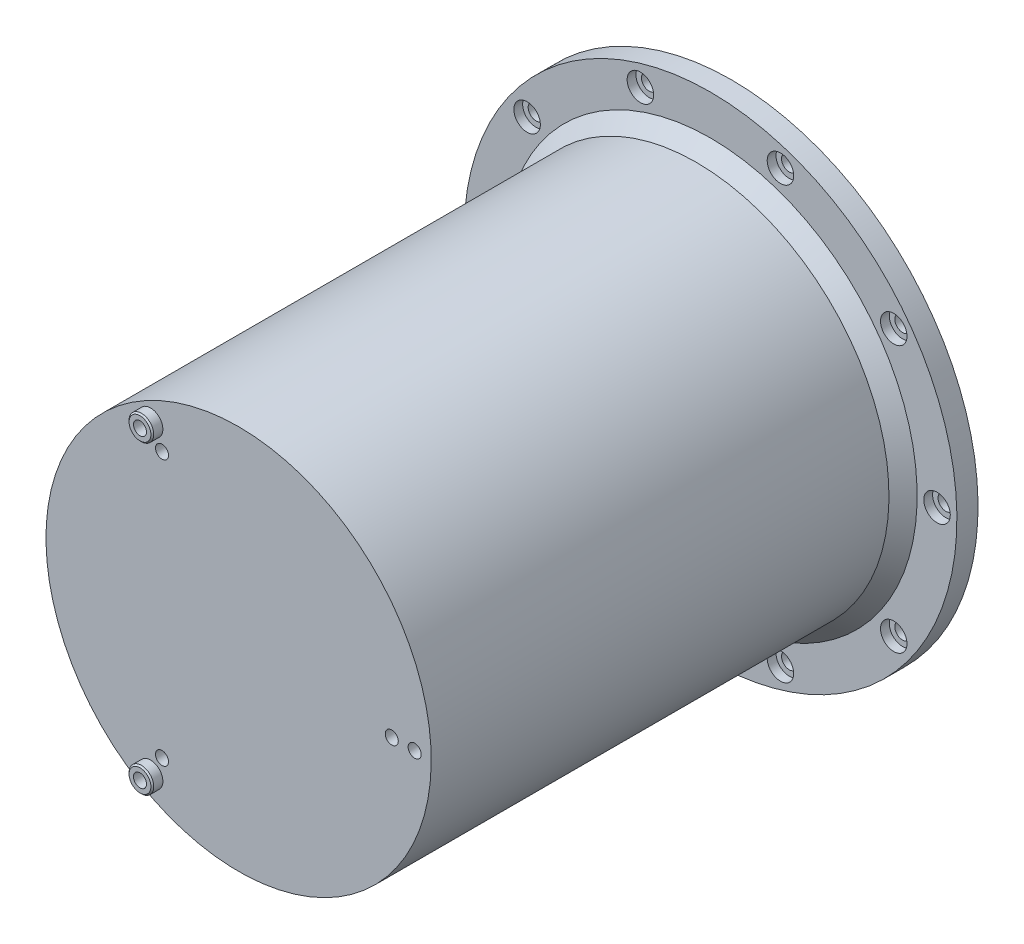
SolidWorks part; units mm, degrees
ref_plane "Piano frontale" through (0, 0, 0) normal (0, 0, 1) x (1, 0, 0)
ref_plane "Piano superiore" through (0, 0, 0) normal (0, 1, 0) x (1, 0, 0)
ref_plane "Piano destro" through (0, 0, 0) normal (1, 0, 0) x (0, 0, -1)
sketch "Schizzo1" plane through (0, 0, -132.2078) normal (0, 0, -1) x (-1, 0, 0)
  circle A14 centre (214.1711, -331.6849) radius 273.5326
  arc A15 (311.7735, -587.2115) -> (380.5507, -548.7976) centre (214.1711, -331.6849) ccw construction
  arc A16 (-35.8289, -322.4349) -> (-35.8289, -340.9349) centre (-35.8289, -331.6849) ccw construction
  arc A17 (-35.8289, -340.9349) -> (-35.8289, -322.4349) centre (-35.8289, -331.6849) ccw construction
  arc A18 (-3.3289, -340.9349) -> (-3.3289, -322.4349) centre (-3.3289, -331.6849) ccw construction
  arc A19 (-3.3289, -322.4349) -> (-3.3289, -340.9349) centre (-3.3289, -331.6849) ccw construction
  arc A20 (322.9211, -134.0744) -> (322.9211, -152.5744) centre (322.9211, -143.3244) ccw construction
  arc A21 (322.9211, -152.5744) -> (322.9211, -134.0744) centre (322.9211, -143.3244) ccw construction
  arc A22 (339.1711, -124.4286) -> (339.1711, -105.9286) centre (339.1711, -115.1786) ccw construction
  arc A23 (339.1711, -105.9286) -> (339.1711, -124.4286) centre (339.1711, -115.1786) ccw construction
  arc A24 (322.9211, -529.2954) -> (322.9211, -510.7954) centre (322.9211, -520.0454) ccw construction
  arc A25 (322.9211, -510.7954) -> (322.9211, -529.2954) centre (322.9211, -520.0454) ccw construction
  arc A26 (339.1711, -557.4413) -> (339.1711, -538.9413) centre (339.1711, -548.1913) ccw construction
  arc A27 (339.1711, -538.9413) -> (339.1711, -557.4413) centre (339.1711, -548.1913) ccw construction
  arc A28 (-35.8289, -322.4349) -> (-35.8289, -340.9349) centre (-35.8289, -331.6849) ccw
  arc A29 (-35.8289, -340.9349) -> (-35.8289, -322.4349) centre (-35.8289, -331.6849) ccw
  arc A30 (-3.3289, -340.9349) -> (-3.3289, -322.4349) centre (-3.3289, -331.6849) ccw
  arc A31 (-3.3289, -322.4349) -> (-3.3289, -340.9349) centre (-3.3289, -331.6849) ccw
  arc A32 (322.9211, -134.0744) -> (322.9211, -152.5744) centre (322.9211, -143.3244) ccw
  arc A33 (322.9211, -152.5744) -> (322.9211, -134.0744) centre (322.9211, -143.3244) ccw
  arc A34 (339.1711, -124.4286) -> (339.1711, -105.9286) centre (339.1711, -115.1786) ccw
  arc A35 (339.1711, -105.9286) -> (339.1711, -124.4286) centre (339.1711, -115.1786) ccw
  arc A36 (322.9211, -529.2954) -> (322.9211, -510.7954) centre (322.9211, -520.0454) ccw
  arc A37 (322.9211, -510.7954) -> (322.9211, -529.2954) centre (322.9211, -520.0454) ccw
  arc A38 (339.1711, -557.4413) -> (339.1711, -538.9413) centre (339.1711, -548.1913) ccw
  arc A39 (339.1711, -538.9413) -> (339.1711, -557.4413) centre (339.1711, -548.1913) ccw
extrude "Estrusione-Estrusione1" add sketch "Schizzo1" along normal blind 15
sketch "Schizzo5" plane through (0, 0, -147.2078) normal (0, 0, -1) x (-1, 0, 0)
  circle A0 centre (214.1711, -331.6849) radius 273.5326 construction
  circle A1 centre (214.1711, -331.6849) radius 273.5326
extrude "Estrusione-Estrusione4" add sketch "Schizzo5" along normal blind 685
sketch "Schizzo6" plane through (0, 0, -832.2078) normal (0, 0, -1) x (-1, 0, 0)
  circle A0 centre (214.1711, -331.6849) radius 350
  dimension "D1" = 700
extrude "Estrusione-Estrusione5" add sketch "Schizzo6" against normal blind 30
chamfer "Smusso2" distance 20 angle 45 1 edges at (-214.1711, -58.1523, -802.2078)
sketch "Schizzo7" plane through (0, 0, -802.2078) normal (0, 0, 1) x (1, 0, 0)
  line L0 (135.8289, -331.6849) -> (107.5952, -331.6849) construction
  line L1 (107.5952, -331.6849) -> (79.3615, -331.6849) construction
  circle A0 centre (-214.1711, -331.6849) radius 321.7663
  circle A1 centre (-214.1711, -331.6849) radius 350 construction
  circle A2 centre (-214.1711, -331.6849) radius 293.5326 construction
  point P11 (107.5952, -331.6849)
hole_wizard "Foro lamato per Bullone M20 a testa esagonale-1" positions "Schizzo3D1" profile "Schizzo9" counterbore size "M20" standard "ISO" end condition through all
sketch3d "Schizzo3D1"
  point P0 (107.5952, -331.6849, -802.2078)
sketch "Schizzo9" plane through (107.5952, -331.6849, -802.2078) normal (1, 0, 0) x (0, -1, 0)
  line L0 (0, 0) -> (0, 30)
  line L1 (0, 30) -> (11, 30)
  line L3 (11, 30) -> (11, 12.5)
  line L4 (11, 12.5) -> (18.8205, 12.5)
  line L5 (18.8205, 12.5) -> (18.8205, 0)
  line L7 (18.8205, 0) -> (0, 0)
  line L11 (0, -6.35) -> (0, 107.95) construction
  dimension "Thru Hole Dia." = 22
  dimension "Thru Hole Depth" = 30
  dimension "C'Bore Dia." = 37.641
  dimension "C'Bore Depth" = 12.5
pattern_circular "RipetizioneCircolare1" count 10 every 36 about axis through (-214.1711, -331.6849, -132.2078) along (0, 0, -1) of "Foro lamato per Bullone M20 a testa esagonale-1"
sketch "Schizzo10" plane through (0, 0, -132.2078) normal (0, 0, 1) x (1, 0, 0)
  arc A0 (-339.1711, -132.6786) -> (-339.1711, -97.6786) centre (-339.1711, -115.1786) ccw construction
  arc A1 (-339.1711, -97.6786) -> (-339.1711, -132.6786) centre (-339.1711, -115.1786) ccw construction
  arc A2 (-339.1711, -565.6913) -> (-339.1711, -530.6913) centre (-339.1711, -548.1913) ccw construction
  arc A3 (-339.1711, -530.6913) -> (-339.1711, -565.6913) centre (-339.1711, -548.1913) ccw construction
  arc A4 (-339.1711, -132.6786) -> (-339.1711, -97.6786) centre (-339.1711, -115.1786) ccw
  arc A5 (-339.1711, -97.6786) -> (-339.1711, -132.6786) centre (-339.1711, -115.1786) ccw
  arc A6 (-339.1711, -565.6913) -> (-339.1711, -530.6913) centre (-339.1711, -548.1913) ccw
  arc A7 (-339.1711, -530.6913) -> (-339.1711, -565.6913) centre (-339.1711, -548.1913) ccw
  circle A8 centre (-339.1711, -548.1913) radius 9.25 construction
  circle A9 centre (-339.1711, -115.1786) radius 9.25 construction
  circle A10 centre (-339.1711, -548.1913) radius 9.25
  circle A11 centre (-339.1711, -115.1786) radius 9.25
extrude "Estrusione-Estrusione6" add sketch "Schizzo10" along normal blind 15
chamfer "Smusso3" distance 2 angle 45 2 edges at (-321.6711, -115.1786, -117.2078) (-321.6711, -548.1913, -117.2078)
